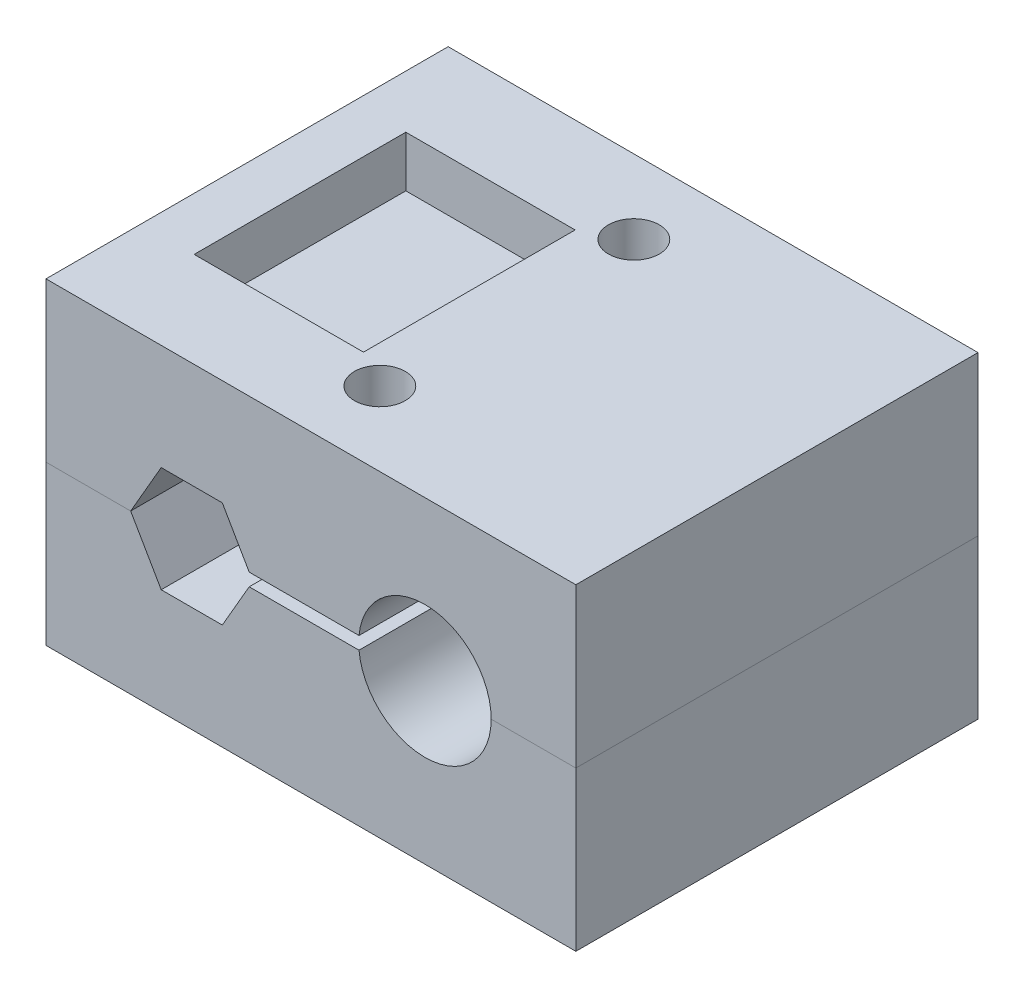
SolidWorks part; units mm, degrees
ref_plane "Front Plane" through (0, 0, 0) normal (0, 0, 1) x (1, 0, 0)
ref_plane "Top Plane" through (0, 0, 0) normal (0, 1, 0) x (1, 0, 0)
ref_plane "Right Plane" through (0, 0, 0) normal (1, 0, 0) x (0, 0, -1)
sketch "Sketch2" plane through (0, 0, 0) normal (0, 0, 1) x (1, 0, 0)
  line L0 (0, 0) -> (0, 0.0003) construction
  line L1 (-10.5073, 0.0003) -> (-8.6743, -3.1747)
  line L2 (-8.6743, -3.1747) -> (-5.0081, -3.1747)
  line L3 (-5.0081, -3.1747) -> (-3.175, 0.0003)
  line L4 (-3.175, 0.0003) -> (-5.0081, 3.1753)
  line L5 (-5.0081, 3.1753) -> (-8.6743, 3.1753)
  line L6 (-8.6743, 3.1753) -> (-10.5073, 0.0003)
  line L9 (-3.175, 0.0003) -> (3.175, 0.0003) construction
  line L11 (-15.5873, 9.5253) -> (16.2052, 9.5253)
  line L12 (-15.5873, 9.5253) -> (-15.5873, -9.5247)
  line L13 (-15.5873, -9.5247) -> (16.2052, -9.5247)
  line L14 (16.2052, 9.5253) -> (16.2052, -9.5247)
  line L16 (-10.5073, 0.0003) -> (-15.5873, 0.0003) construction
  circle A0 centre (-6.8412, 0.0003) radius 3.175 construction
  circle A1 centre (7.1501, 0.0003) radius 3.9751
  point P10 (3.175, 0.0003)
  point P13 (11.1252, 0.0003)
  point P25 (0, -15.0238)
  dimension "D2" = 7.9502
  dimension "D1" = 6.35
  dimension "D3" = 6.35
  dimension "D4" = 0.0003
  dimension "D5" = 5.08
  dimension "D6" = 6.35
  dimension "D7" = 6.35
  dimension "D8" = 5.08
  dimension "D9" = 31.7925
extrude "Boss-Extrude3" add sketch "Sketch2" along normal mid plane 24.13
sketch "Sketch7" plane through (0, 0, 0) normal (0, 1, 0) x (1, 0, 0)
  line L0 (-15.5873, -12.065) -> (-15.5873, 12.065) construction
  line L2 (-12.4123, -6.35) -> (-2.2523, -6.35)
  line L3 (-12.4123, -6.35) -> (-12.4123, 6.35)
  line L4 (-12.4123, 6.35) -> (-2.2523, 6.35)
  line L5 (-2.2523, -6.35) -> (-2.2523, 6.35)
  line L6 (-12.4123, -6.35) -> (-2.2523, 6.35) construction
  line L8 (0, 0) -> (0, 7.62) construction
  line L10 (0, -7.62) -> (0, 0) construction
  line L12 (-12.4123, 6.35) -> (-2.2523, -6.35) construction
  circle A0 centre (0, -7.62) radius 1.524
  circle A1 centre (0, 7.62) radius 1.524
  point P5 (-7.3323, 0)
  point P10 (0, 9.144)
  point P11 (0, -9.144)
  dimension "D1" = 3.048
  dimension "D2" = 12.7
  dimension "D3" = 10.16
  dimension "D4" = 7.62
  dimension "D5" = 3.175
extrude "Cut-Extrude5" cut sketch "Sketch7" against normal through all and the other way through all contours A1 | A0
extrude "Cut-Extrude7" cut sketch "Sketch7<6>" against normal blind 3.048 from surface contours L2 L5 L4 L3 region at (-7.3323, 0, 0) starting at face at (0, 9.5253, 9.144)
sketch "Sketch7<6>" plane through (0, 0, 0) normal (0, 1, 0) x (1, 0, 0) same geometry as "Sketch7"
sketch "Sketch8" plane through (0, 0, 0) normal (0, 0, 1) x (1, 0, 0)
  line L1 (-6.35, -0.381) -> (6.35, -0.381)
  line L2 (-6.35, -0.381) -> (-6.35, 0.381)
  line L3 (-6.35, 0.381) -> (6.35, 0.381)
  line L4 (6.35, -0.381) -> (6.35, 0.381)
  line L5 (-6.35, -0.381) -> (6.35, 0.381) construction
  line L6 (-6.35, 0.381) -> (6.35, -0.381) construction
  point P0 (0, 0)
  dimension "D1" = 0.762
  dimension "D2" = 12.7
extrude "Cut-Extrude8" cut sketch "Sketch8" against normal through all and the other way through all
split "Split3" trim tools "Top Plane" bodies to split 117 resulting bodies 118 119
